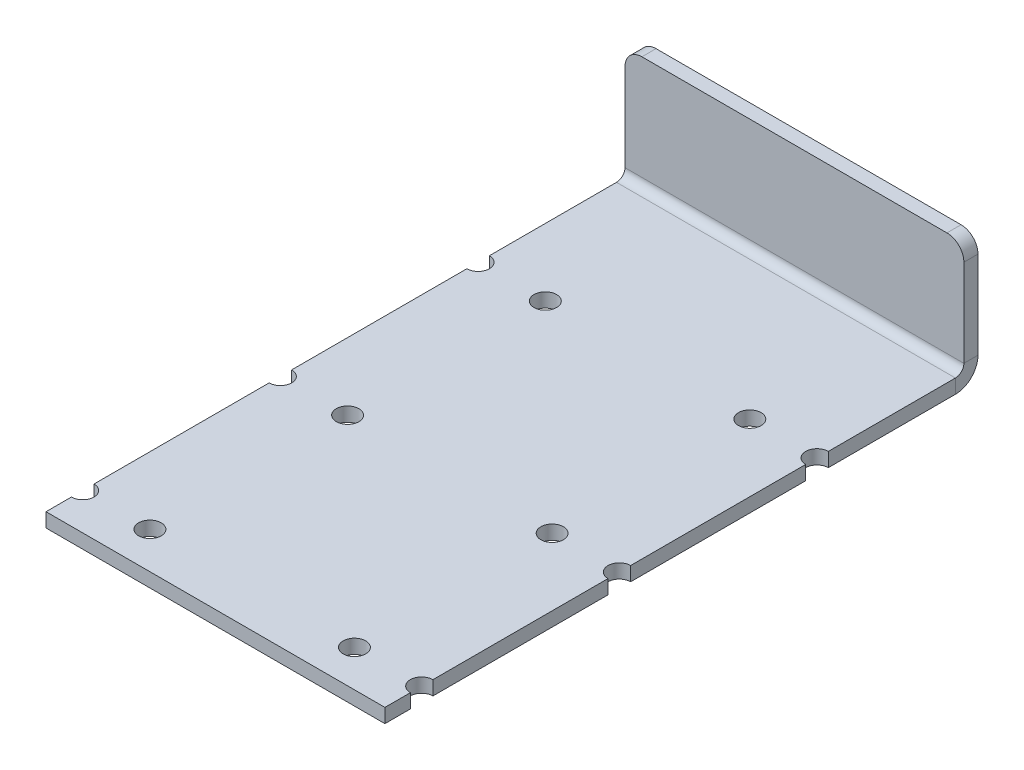
SolidWorks part; units mm, degrees
note: The reader was unsure of these and kept them because the rebuilt part matched: flange length of "Edge-Flange3".
material "1345 Alloy"
ref_plane "Front Plane" through (0, 0, 0) normal (0, 0, 1) x (1, 0, 0)
ref_plane "Top Plane" through (0, 0, 0) normal (0, 1, 0) x (1, 0, 0)
ref_plane "Right Plane" through (0, 0, 0) normal (1, 0, 0) x (0, 0, -1)
sketch "Sketch1" plane through (0, 0, 0) normal (0, 0, 1) x (1, 0, 0)
  line L27 (60, 66.5) -> (60, 100.5)
  line L28 (-60, 66.5) -> (-60, 100.5)
  line L29 (-54, 106.5) -> (54, 106.5)
  line L30 (-60, 66.5) -> (60, 66.5)
  arc A2 (60, 100.5) -> (54, 106.5) centre (54, 100.5) ccw
  arc A3 (-54, 106.5) -> (-60, 100.5) centre (-54, 100.5) ccw
  point P0 (0, 0)
  point P22 (60, 106.5)
  dimension "D1" = 40
base flange "Base-Flange2" sketch "Sketch1" thickness 5 reverse thickness direction yes parameters "D1"=0.7366
edge flange "Edge-Flange3" sketch "Sketch17" flange angle 90 flange length 210 flange position material outside bend radius 3 thickness 5 relief rectangular parameters "D6"=10
sketch "Sketch17" plane through (0, 66.5, 5) normal (0, -1, 0) x (1, 0, 0)
  line L0 (-60, 0) -> (60, 0) construction
  line L1 (-60, 0) -> (60, 0)
  line L2 (-60, 0) -> (-60, 205)
  line L3 (-60, 205) -> (60, 205)
  line L4 (60, 205) -> (60, 0)
bend "EdgeBend3" bend radius 3 bend angle 90 parameters "D5"=1
sketch "Sketch18" plane through (0, 66.5, 0) normal (0, 1, 0) x (1, 0, 0)
  line L0 (0, 0) -> (0, -57) construction
  line L1 (0, -57) -> (36.205, -57) construction
  line L2 (0, -57) -> (-36.205, -57) construction
  circle A0 centre (36.205, -197) radius 4
  circle A1 centre (-36.205, -197) radius 4
  circle A2 centre (-36.205, -127) radius 4
  circle A3 centre (36.205, -127) radius 4
  circle A4 centre (36.205, -57) radius 4
  circle A5 centre (-36.205, -57) radius 4
  circle A6 centre (-60, -197) radius 4
  circle A7 centre (-60, -127) radius 4
  circle A8 centre (-60, -57) radius 4
  circle A9 centre (60, -197) radius 4
  circle A10 centre (60, -127) radius 4
  circle A11 centre (60, -57) radius 4
  dimension "D1" = 8
  dimension "D2" = 8
  dimension "D3" = 8
  dimension "D4" = 8
  dimension "D5" = 57
  dimension "D6" = 36.205
  dimension "D7" = 36.205
extrude "Cut-Extrude1" cut sketch "Sketch18" against normal blind 10 normal cut yes
sketch "Bend-Lines5" [suppressed] plane through (0, 0, 0) normal (0, 1, 0) x (1, 0, 0)
sketch "Bounding-Box5" [suppressed] plane through (0, 0, 0) normal (0, 1, 0) x (1, 0, 0)
sheet metal parameters "Sheet-Metal14" thickness 5 parameters "D1"=0.7366
flat pattern "Flat-Pattern14" [suppressed]
sketch "Bend-Lines6" plane through (0, 0, 0) normal (0, 0, -1) x (-1, 0, 0)
sketch3d "Bounding-Box6" [suppressed]
  line L0 (-6, -143, 0) -> (-6, 6, 0) construction
  line L1 (114, -143, 0) -> (114, 6, 0) construction
  line L2 (-6, -143, 0) -> (114, -143, 0) construction
  line L3 (-6, 6, 0) -> (114, 6, 0) construction
sketch "Sketch11-1" [suppressed] plane through (0, 0, 5) normal (0, 0, 1) x (1, 0, 0)
  line L1 (0, 106.5) -> (0, -30.5934) construction
  line L4 (-60, -30.5934) -> (60, -30.5934)
sheet metal parameters "Sheet-Metal16" thickness 5 parameters "D1"=0.7366
flat pattern "Flat-Pattern14"
sketch "Bend-Lines6" plane through (0, 0, 0) normal (0, 0, -1) x (-1, 0, 0)
  line L0 (-60, 84.6946) -> (60, 84.6946) construction
  line L1 (-60, 84.6946) -> (60, 84.6946) construction
sketch3d "Bounding-Box6" [suppressed]
  line L0 (-6, -222.6108, 0) -> (-6, 6, 0) construction
  line L1 (114, -222.6108, 0) -> (114, 6, 0) construction
  line L2 (-6, -222.6108, 0) -> (114, -222.6108, 0) construction
  line L3 (-6, 6, 0) -> (114, 6, 0) construction
bend of the flat pattern "Flatten-<EdgeBend3>1"
sheet metal parameters "Sheet-Metal21" thickness 5 parameters "D1"=0.7366
flat pattern "Flat-Pattern14"
sketch "Bend-Lines6" plane through (0, 0, 0) normal (0, 0, -1) x (-1, 0, 0)
  line L0 (-60, 65.9229) -> (60, 65.9229) construction
  line L1 (-60, 65.9229) -> (60, 65.9229) construction
sketch3d "Bounding-Box6" [suppressed]
  line L0 (-6, -240.1542, 0) -> (-6, 6, 0) construction
  line L1 (114, -240.1542, 0) -> (114, 6, 0) construction
  line L2 (-6, -240.1542, 0) -> (114, -240.1542, 0) construction
  line L3 (-6, 6, 0) -> (114, 6, 0) construction
bend of the flat pattern "Flatten-<EdgeBend3>1"
